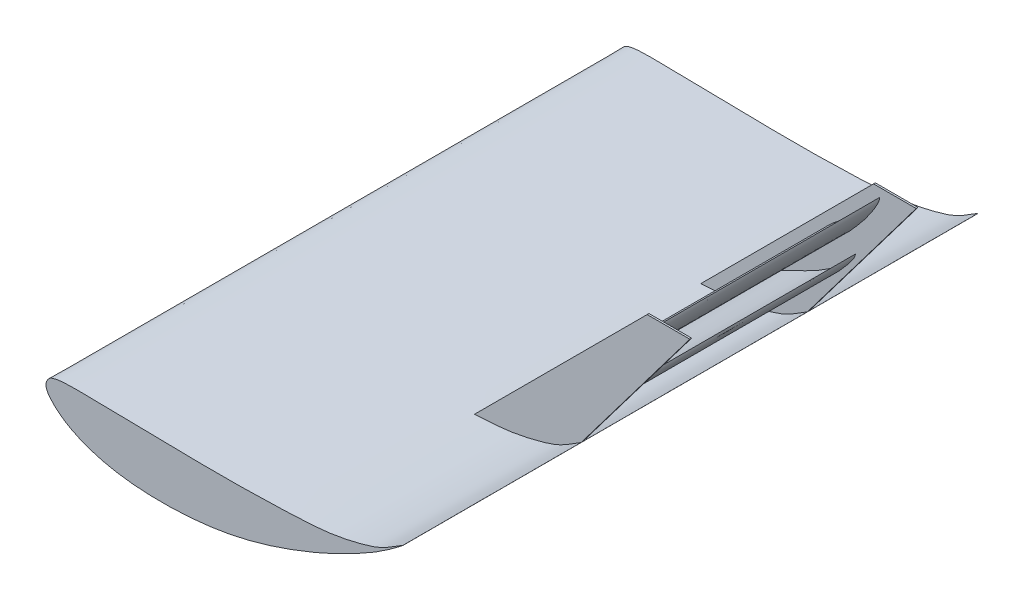
SolidWorks part; units mm, degrees
ref_plane "Front Plane" through (0, 0, 0) normal (0, 0, 1) x (1, 0, 0)
ref_plane "Top Plane" through (0, 0, 0) normal (0, 1, 0) x (1, 0, 0)
ref_plane "Right Plane" through (0, 0, 0) normal (1, 0, 0) x (0, 0, -1)
sketch "Sketch1" plane through (0, 0, 0) normal (0, 0, 1) x (1, 0, 0)
  line L0 (0, 0) -> (100, 0) construction
  line L1 (1.25, 16.6531) -> (1.25, -38.4553) construction
  line L2 (2.5, 17.9055) -> (2.5, -38.4614) construction
  line L3 (0, 16.6233) -> (0, -25.6938) construction
  line L4 (2.5, -38.4553) -> (2.5, 17.9055) construction
  line L6 (5, 17.9055) -> (5, -38.4553) construction
  line L8 (7.5, -38.4553) -> (7.5, 17.9055) construction
  line L10 (10, 17.9055) -> (10, -38.4553) construction
  line L12 (15, -38.4553) -> (15, 17.9055) construction
  line L14 (20, 17.9055) -> (20, -38.4553) construction
  line L16 (30, -38.4553) -> (30, 17.9055) construction
  line L18 (40, 17.9055) -> (40, -38.4553) construction
  line L20 (50, -38.4553) -> (50, 17.9055) construction
  line L22 (60, 17.9055) -> (60, -38.4553) construction
  line L24 (70, -38.4553) -> (70, 17.9055) construction
  line L26 (80, 17.9055) -> (80, -38.4553) construction
  line L28 (90, -38.4553) -> (90, 17.9055) construction
  line L30 (95, 17.9055) -> (95, -38.4553) construction
  line L32 (100, -38.4553) -> (100, 17.9055) construction
  spline S2 degree 3 poles (94.3673, -3.5638) (102.8561, 1.5222) (94.504, -2.988) (88.8138, -4.3065) (79.9056, -5.4947) (70.0198, -5.0741) (59.9849, -4.387) (49.9902, -3.5342) (39.9927, -2.4103) (30.0039, -1.1606) (21.6652, -0.2167) (14.9997, 0.5924) (10.0103, 1.184) (5.8366, 1.6528) (2.898, 1.5692) (0.8648, 1.1108) (-0.6238, -1.2668) (0.9385, -3.7627) (2.7533, -5.9838) (4.8768, -7.8493) (7.4255, -9.5789) (10.7358, -11.3943) (14.9019, -13.1207) (21.5668, -15.0457) (29.9416, -16.4142) (39.9918, -17.0298) (50.051, -16.6825) (60.0771, -15.2123) (70.1301, -12.7919) (80.007, -9.774) (88.8716, -6.1499) (94.3673, -3.5638) (102.8561, 1.5222) (94.504, -2.988) knots -0.105257 -0.054131 -0.027635 0 0.026268 0.051016 0.098804 0.146246 0.193788 0.241403 0.289125 0.336907 0.384666 0.408554 0.432437 0.456234 0.468112 0.474323 0.485191 0.50162 0.510955 0.52691 0.541278 0.554823 0.580548 0.60527 0.653411 0.700937 0.748406 0.796324 0.845052 0.894743 0.945869 0.972365 1 1.026268 1.051016 1.098804 only from (100, -0.1) to (100, -0.1)
  point P37 (0, -0.86)
  point P38 (1.25, -4.09)
  point P40 (1.25, 1.06)
  point P41 (2.5, 1.45)
  point P42 (5, -7.86)
  point P43 (2.5, -5.61)
  point P44 (5, 1.59)
  point P45 (7.5, -9.57)
  point P46 (7.5, 1.44)
  point P47 (10, 1.18)
  point P48 (15, 0.59)
  point P49 (15, -13.05)
  point P50 (20, -0.01)
  point P51 (20, -14.52)
  point P52 (30, -1.18)
  point P53 (30, -16.25)
  point P54 (40, -2.39)
  point P55 (10, -10.95)
  point P56 (40, -16.87)
  point P57 (40, -2.39)
  point P58 (50, -3.49)
  point P59 (50, -16.5)
  point P60 (60, -4.36)
  point P61 (60, -15.07)
  point P62 (70, -5.03)
  point P63 (70, -12.72)
  point P64 (80, -5.19)
  point P65 (80, -9.6)
  point P66 (90, -3.97)
  point P67 (90, -5.58)
  point P68 (95, -2.48)
  point P69 (95, -3.09)
  point P70 (100, -0.1)
  point P71 (100, -0.2)
  dimension "D1" = 100
  dimension "D2" = 1.25
  dimension "D3" = 2.5
  dimension "D4" = 2.5
  dimension "D5" = 7.5
  dimension "D6" = 10
  dimension "D7" = 15
  dimension "D8" = 5
  dimension "D9" = 10
  dimension "D10" = 10
  dimension "D11" = 10
  dimension "D12" = 10
  dimension "D13" = 10
  dimension "D14" = 10
  dimension "D15" = 10
  dimension "D16" = 5
  dimension "D17" = 5
curve "Curve1"
  spline degree 3 poles (98.5502, -0.8292, 0) (100.5299, 0.3794, 0) (99.1462, -0.6768, 0) (98.4443, -1.2755, 0) (97.3097, -2.0642, 0) (96.0009, -2.7117, 0) (94.4298, -3.3947, 0) (92.569, -4.0837, 0) (90.4012, -4.8122, 0) (87.9505, -5.5478, 0) (85.2749, -6.304, 0) (82.4359, -7.0338, 0) (79.5022, -7.7406, 0) (76.5208, -8.4057, 0) (73.5219, -9.0393, 0) (70.5175, -9.6161, 0) (67.5077, -10.1489, 0) (64.4881, -10.6321, 0) (61.4395, -11.0484, 0) (58.3521, -11.4274, 0) (55.2125, -11.781, 0) (52.0112, -12.0861, 0) (48.7533, -12.37, 0) (45.4544, -12.6663, 0) (42.1402, -12.9291, 0) (38.8572, -13.1898, 0) (35.6511, -13.4329, 0) (32.5711, -13.6325, 0) (29.6613, -13.7858, 0) (26.9506, -13.8772, 0) (24.4353, -13.8571, 0) (22.088, -13.7476, 0) (19.8826, -13.5013, 0) (17.7867, -13.168, 0) (15.7934, -12.7056, 0) (13.8906, -12.1349, 0) (12.076, -11.4655, 0) (10.3558, -10.6964, 0) (8.7488, -9.8421, 0) (7.2684, -8.933, 0) (5.9416, -8.0004, 0) (4.7755, -7.0863, 0) (3.7847, -6.217, 0) (2.957, -5.4094, 0) (2.269, -4.6735, 0) (1.728, -3.9816, 0) (1.2751, -3.3596, 0) (0.9309, -2.7719, 0) (0.6318, -2.2442, 0) (0.4105, -1.7465, 0) (0.2408, -1.2843, 0) (0.1068, -0.8552, 0) (0.0223, -0.45, 0) (-0.004, -0.0672, 0) (-0.0039, 0.3013, 0) (0.0809, 0.6622, 0) (0.2952, 0.9824, 0) (0.6315, 1.1995, 0) (1.032, 1.3336, 0) (1.4872, 1.4186, 0) (2.0055, 1.4764, 0) (2.6028, 1.5163, 0) (3.3032, 1.5313, 0) (4.1367, 1.5461, 0) (5.1573, 1.5223, 0) (6.4269, 1.4548, 0) (8.0274, 1.3654, 0) (10.0021, 1.2291, 0) (12.3384, 1.004, 0) (14.971, 0.7256, 0) (17.8195, 0.3367, 0) (20.844, -0.1077, 0) (24.0032, -0.6376, 0) (27.2668, -1.1722, 0) (30.5738, -1.7172, 0) (33.8785, -2.2723, 0) (37.1527, -2.7975, 0) (40.3807, -3.3138, 0) (43.5644, -3.7828, 0) (46.6972, -4.2145, 0) (49.7874, -4.5959, 0) (52.8339, -4.9281, 0) (55.8477, -5.1987, 0) (58.8316, -5.4085, 0) (61.7919, -5.5626, 0) (64.7329, -5.6385, 0) (67.6568, -5.6622, 0) (70.5644, -5.6128, 0) (73.4581, -5.4881, 0) (76.3366, -5.3163, 0) (79.1931, -5.05, 0) (82.0171, -4.7312, 0) (84.7804, -4.3625, 0) (87.434, -3.9036, 0) (89.9332, -3.4404, 0) (92.2075, -2.9247, 0) (94.233, -2.3848, 0) (95.9446, -1.8589, 0) (97.5056, -1.2357, 0) (98.5502, -0.8292, 0) (100.5299, 0.3794, 0) (99.1462, -0.6768, 0) knots -0.020778 -0.013318 -0.006872 0 0.003934 0.00967 0.015849 0.022782 0.030794 0.040273 0.051195 0.063508 0.076888 0.09098 0.105453 0.12007 0.134692 0.149314 0.163846 0.178433 0.193072 0.207875 0.222946 0.238282 0.253894 0.269743 0.28568 0.30147 0.316872 0.331691 0.345638 0.35857 0.370496 0.381625 0.392182 0.402235 0.411978 0.42144 0.430647 0.439636 0.448385 0.456672 0.46448 0.47158 0.477867 0.483331 0.488125 0.492267 0.495894 0.499125 0.502007 0.504569 0.506909 0.509051 0.510997 0.512815 0.514533 0.516257 0.518043 0.519896 0.521872 0.524061 0.526511 0.529332 0.532624 0.536536 0.54126 0.547229 0.554731 0.564199 0.575553 0.588316 0.602079 0.616691 0.632061 0.647918 0.664017 0.680023 0.695872 0.71147 0.726804 0.741922 0.756725 0.771359 0.785775 0.800025 0.814163 0.828192 0.842121 0.856004 0.869802 0.883566 0.897265 0.910851 0.924235 0.937151 0.949387 0.960589 0.970563 0.979222 0.986682 0.993128 1 1.003934 1.00967 1.015849 periodic
sketch "Sketch2" plane through (0, 0, 0) normal (0, 0, 1) x (1, 0, 0)
  line L0 (331.6325, -0.1558) -> (-65.7962, -45.4371) construction
  line L1 (-65.7962, -45.4371) -> (-68.337, -23.1365) construction
  line L2 (0, 0) -> (60.5483, 0) construction
  line L3 (385.2571, 82.501) -> (286.9589, 13.6718) construction
  line L4 (286.9589, 13.6718) -> (272.478, 34.3526) construction
  line L5 (331.6325, -0.1558) -> (331.6325, 76.9311) construction
  line L6 (331.6325, -0.1558) -> (397.2706, -0.1558) construction
  line L7 (412.1546, 150.4845) -> (355.5861, 93.9159) construction
  line L8 (299.294, 9.8442) -> (308.8152, 9.8442) construction
  line L9 (286.6325, 14.5606) -> (286.6325, 26.1748) construction
  line L10 (355.5861, 93.9159) -> (325.5679, 123.9341) construction
  line L11 (385.2571, 82.501) -> (439.2948, 82.501) construction
  line L12 (385.2571, 82.501) -> (385.2571, 253.7541) construction
  line L14 (360.5365, 92.501) -> (347.2815, 92.501) construction
  line L15 (355.2571, 94.5953) -> (355.2571, 86.9128) construction
  spline S1 degree 3 poles (384.8846, 81.2478) (385.5164, 83.2388) (384.4039, 80.6874) (383.6577, 79.5684) (382.5534, 77.8807) (381.234, 76.1849) (379.6159, 74.2589) (377.7366, 72.1854) (375.6004, 70.0085) (373.3094, 67.7296) (370.8484, 65.4636) (368.2936, 63.2048) (365.6704, 60.9752) (362.9606, 58.8233) (360.2036, 56.7073) (357.3809, 54.6556) (354.4918, 52.6644) (351.55, 50.7129) (348.5353, 48.8248) (345.4591, 46.9752) (342.3116, 45.1647) (339.0895, 43.3924) (335.7907, 41.6382) (332.4153, 39.904) (328.9642, 38.1714) (325.437, 36.4548) (321.8583, 34.7152) (318.229, 32.9837) (314.6045, 31.2409) (311.0296, 29.5177) (307.5607, 27.8619) (304.283, 26.2148) (301.2163, 24.6344) (298.438, 23.0944) (295.9876, 21.7059) (293.9535, 20.4794) (292.3194, 19.4647) (291.0255, 18.6563) (290.0064, 17.9765) (289.1977, 17.3878) (288.5198, 16.8905) (287.9605, 16.4397) (287.4911, 16.026) (287.1025, 15.6288) (286.8013, 15.2211) (286.6204, 14.7762) (286.6306, 14.3139) (286.7959, 13.9009) (287.0496, 13.5387) (287.3391, 13.1808) (287.7014, 12.8408) (288.1286, 12.5116) (288.6138, 12.1745) (289.1741, 11.8379) (289.8315, 11.5255) (290.5746, 11.1852) (291.4481, 10.8861) (292.4563, 10.579) (293.6392, 10.33) (295.0088, 10.1068) (296.5811, 9.9353) (298.3566, 9.8405) (300.3027, 9.8384) (302.3835, 9.9651) (304.5509, 10.2329) (306.7709, 10.6623) (309.0149, 11.2548) (311.2776, 12.005) (313.5546, 12.9239) (315.8434, 14.0403) (318.1798, 15.3178) (320.5616, 16.8273) (323.0467, 18.5404) (325.647, 20.4977) (328.4002, 22.653) (331.2889, 24.971) (334.2713, 27.4186) (337.3173, 29.9365) (340.3924, 32.4781) (343.4295, 35.0419) (346.4347, 37.5652) (349.3698, 40.0706) (352.2108, 42.5809) (354.9831, 45.0803) (357.6916, 47.5896) (360.3254, 50.1446) (362.9155, 52.7417) (365.4699, 55.3783) (367.9798, 58.0668) (370.4509, 60.7742) (372.8463, 63.4898) (375.1328, 66.1627) (377.2406, 68.7489) (379.1415, 71.1601) (380.7696, 73.3693) (382.1232, 75.3282) (383.1961, 77.0817) (384.0359, 78.6195) (384.6074, 80.1761) (384.8846, 81.2478) (385.5164, 83.2388) (384.4039, 80.6874) knots -0.015849 -0.00967 -0.003934 0 0.006872 0.013318 0.020778 0.029437 0.039411 0.050613 0.062849 0.075765 0.089149 0.102735 0.116434 0.130198 0.143996 0.157879 0.171808 0.185837 0.199975 0.214225 0.228641 0.243275 0.258078 0.273196 0.28853 0.304128 0.319977 0.335983 0.352082 0.367939 0.383309 0.397921 0.411684 0.424447 0.435801 0.445269 0.452771 0.45874 0.463464 0.467376 0.470668 0.473489 0.475939 0.478128 0.480104 0.481957 0.483743 0.485467 0.487185 0.489003 0.490949 0.493091 0.495431 0.497993 0.500875 0.504106 0.507733 0.511875 0.516669 0.522133 0.52842 0.53552 0.543328 0.551615 0.560364 0.569353 0.57856 0.588022 0.597765 0.607818 0.618375 0.629504 0.64143 0.654362 0.668309 0.683128 0.69853 0.71432 0.730257 0.746106 0.761718 0.777054 0.792125 0.806928 0.821567 0.836154 0.850686 0.865308 0.87993 0.894547 0.90902 0.923112 0.936492 0.948805 0.959727 0.969206 0.977218 0.984151 0.99033 0.996066 1 1.006872 1.013318 1.020778 only from (385.2571, 82.501) to (385.2571, 82.501)
  spline S2 degree 3 poles (310.6391, -16.2329) (342.3319, 7.4626) (310.948, -13.8864) (288.8507, -21.4531) (253.8988, -29.8144) (214.402, -32.1744) (174.2032, -33.5355) (134.0967, -34.2209) (93.8685, -33.8291) (53.6236, -32.9335) (20.0676, -32.5806) (-6.7778, -32.082) (-26.867, -31.764) (-43.661, -31.6021) (-55.3165, -33.1337) (-63.2173, -35.7866) (-68.169, -45.8522) (-60.9356, -55.1433) (-52.8102, -63.238) (-43.602, -69.7925) (-32.7577, -75.633) (-18.8487, -81.5041) (-1.572, -86.6718) (25.7261, -91.6102) (59.5991, -93.6371) (99.8297, -91.9854) (139.7029, -86.4995) (178.9865, -76.5608) (217.9897, -62.8307) (256.0482, -46.7957) (289.8325, -28.7623) (310.6391, -16.2329) (342.3319, 7.4626) (310.948, -13.8864) knots -0.105257 -0.054131 -0.027635 0 0.026268 0.051016 0.098804 0.146246 0.193788 0.241403 0.289125 0.336907 0.384666 0.408554 0.432437 0.456234 0.468112 0.474323 0.485191 0.50162 0.510955 0.52691 0.541278 0.554823 0.580548 0.60527 0.653411 0.700937 0.748406 0.796324 0.845052 0.894743 0.945869 0.972365 1 1.026268 1.051016 1.098804 only from (331.6325, -0.1558) to (331.6325, -0.1558)
  spline S3 degree 3 poles (412.0551, 149.6186) (412.2394, 150.9988) (411.8044, 149.195) (411.444, 148.3739) (410.9144, 147.1381) (410.2444, 145.8719) (409.4051, 144.4202) (408.4113, 142.8413) (407.2608, 141.1648) (406.0205, 139.4033) (404.6671, 137.6307) (403.2512, 135.852) (401.7872, 134.0845) (400.2572, 132.358) (398.692, 130.6496) (397.0763, 128.9757) (395.41, 127.334) (393.7045, 125.7123) (391.9439, 124.1236) (390.1384, 122.5532) (388.2815, 121.0002) (386.3712, 119.4635) (384.4085, 117.9299) (382.3932, 116.4006) (380.328, 114.8636) (378.211, 113.3282) (376.0628, 111.7718) (373.8805, 110.2149) (371.7026, 108.6511) (369.5551, 107.1059) (367.4692, 105.6172) (365.508, 104.1564) (363.6776, 102.7638) (362.0318, 101.4311) (360.5837, 100.2358) (359.3903, 99.1951) (358.4349, 98.3397) (357.6789, 97.6592) (357.0886, 97.0949) (356.6258, 96.6148) (356.2383, 96.2098) (355.9233, 95.8491) (355.663, 95.5231) (355.4538, 95.2174) (355.3033, 94.9148) (355.236, 94.6018) (355.2962, 94.2995) (355.4525, 94.0475) (355.6611, 93.839) (355.8926, 93.6376) (356.1697, 93.4563) (356.4883, 93.2896) (356.846, 93.1244) (357.2528, 92.9683) (357.7205, 92.8393) (358.2478, 92.7019) (358.8559, 92.6067) (359.5534, 92.5218) (360.3589, 92.4952) (361.2839, 92.5073) (362.336, 92.5766) (363.5127, 92.72) (364.7906, 92.9439) (366.142, 93.2679) (367.534, 93.6947) (368.9418, 94.2336) (370.3465, 94.8823) (371.7452, 95.6368) (373.1338, 96.5037) (374.5072, 97.5017) (375.8933, 98.6108) (377.2822, 99.8777) (378.7155, 101.29) (380.1961, 102.8761) (381.7542, 104.6099) (383.3824, 106.4662) (385.0571, 108.4184) (386.7654, 110.4241) (388.4901, 112.4487) (390.1873, 114.4835) (391.8682, 116.4881) (393.5052, 118.4728) (395.0798, 120.4498) (396.6106, 122.4116) (398.0983, 124.3726) (399.5317, 126.355) (400.9316, 128.3599) (402.3034, 130.3867) (403.6401, 132.4423) (404.949, 134.5059) (406.2072, 136.5661) (407.399, 138.5857) (408.4835, 140.5277) (409.4524, 142.3307) (410.2655, 143.9697) (410.9274, 145.4124) (411.4289, 146.6879) (411.8022, 147.7947) (411.9972, 148.8829) (412.0551, 149.6186) (412.2394, 150.9988) (411.8044, 149.195) knots -0.015849 -0.00967 -0.003934 0 0.006872 0.013318 0.020778 0.029437 0.039411 0.050613 0.062849 0.075765 0.089149 0.102735 0.116434 0.130198 0.143996 0.157879 0.171808 0.185837 0.199975 0.214225 0.228641 0.243275 0.258078 0.273196 0.28853 0.304128 0.319977 0.335983 0.352082 0.367939 0.383309 0.397921 0.411684 0.424447 0.435801 0.445269 0.452771 0.45874 0.463464 0.467376 0.470668 0.473489 0.475939 0.478128 0.480104 0.481957 0.483743 0.485467 0.487185 0.489003 0.490949 0.493091 0.495431 0.497993 0.500875 0.504106 0.507733 0.511875 0.516669 0.522133 0.52842 0.53552 0.543328 0.551615 0.560364 0.569353 0.57856 0.588022 0.597765 0.607818 0.618375 0.629504 0.64143 0.654362 0.668309 0.683128 0.69853 0.71432 0.730257 0.746106 0.761718 0.777054 0.792125 0.806928 0.821567 0.836154 0.850686 0.865308 0.87993 0.894547 0.90902 0.923112 0.936492 0.948805 0.959727 0.969206 0.977218 0.984151 0.99033 0.996066 1 1.006872 1.013318 1.020778 only from (412.1546, 150.4845) to (412.1546, 150.4845)
  dimension "D2" = 400
  dimension "D1" = 90
  dimension "D3" = 6.5
  dimension "D4" = 90
  dimension "D5" = 120
  dimension "D6" = 35
  dimension "D7" = 10
  dimension "D8" = 45
  dimension "D9" = 90
  dimension "D10" = 80
  dimension "D11" = 45
  dimension "D12" = 30
  dimension "D13" = 10
extrude "Boss-Extrude1" add sketch "Sketch2" along normal blind 450 and the other way blind 190 contours S2
extrude "Boss-Extrude2" add sketch "Sketch2<3>" along normal blind 250 separate body contours S1
sketch "Sketch2<3>" plane through (0, 0, 0) normal (0, 0, 1) x (1, 0, 0) same geometry as "Sketch2"
extrude "Boss-Extrude3" add sketch "Sketch2<4>" along normal blind 250 separate body contours S3
sketch "Sketch2<4>" plane through (0, 0, 0) normal (0, 0, 1) x (1, 0, 0) same geometry as "Sketch2"
sketch "Sketch3" plane through (0, 0, 0) normal (0, 0, 1) x (1, 0, 0)
  line L0 (213.126, -32.0618) -> (405.3691, 160.1813)
  line L1 (405.3691, 160.1813) -> (452.8645, 160.1813)
  line L2 (452.8645, 160.1813) -> (331.6325, -0.1558)
  spline S0 degree 3 poles (310.6391, -16.2329) (342.3319, 7.4626) (310.948, -13.8864) (288.8507, -21.4531) (253.8988, -29.8144) (214.402, -32.1744) (174.2032, -33.5355) (134.0967, -34.2209) (93.8685, -33.8291) (53.6236, -32.9335) (20.0676, -32.5806) (-6.7778, -32.082) (-26.867, -31.764) (-43.661, -31.6021) (-55.3165, -33.1337) (-63.2173, -35.7866) (-68.169, -45.8522) (-60.9356, -55.1433) (-52.8102, -63.238) (-43.602, -69.7925) (-32.7577, -75.633) (-18.8487, -81.5041) (-1.572, -86.6718) (25.7261, -91.6102) (59.5991, -93.6371) (99.8297, -91.9854) (139.7029, -86.4995) (178.9865, -76.5608) (217.9897, -62.8307) (256.0482, -46.7957) (289.8325, -28.7623) (310.6391, -16.2329) (342.3319, 7.4626) (310.948, -13.8864) knots -0.105257 -0.054131 -0.027635 0 0.026268 0.051016 0.098804 0.146246 0.193788 0.241403 0.289125 0.336907 0.384666 0.408554 0.432437 0.456234 0.468112 0.474323 0.485191 0.50162 0.510955 0.52691 0.541278 0.554823 0.580548 0.60527 0.653411 0.700937 0.748406 0.796324 0.845052 0.894743 0.945869 0.972365 1 1.026268 1.051016 1.098804 only from (331.6325, -0.1558) to (331.6325, -0.1558) construction
  spline S1 degree 3 poles (331.6325, -0.1558) (331.3048, -0.0386) (310.948, -13.8864) (288.8507, -21.4531) (253.8988, -29.8144) (227.165, -31.4118) (213.5191, -32.0438) (213.126, -32.0618) knots 0 0 0 0 0.026268 0.051016 0.098804 0.146246 0.147653 0.147653 0.147653 0.147653
extrude "Boss-Extrude4" add sketch "Sketch3" against normal blind 2
ref_plane "Plane1" through (0, 0, 125) normal (0, 0, 1) x (1, 0, 0)
mirror "Mirror1" about plane through (0, 0, 125) normal (0, 0, 1) of "Boss-Extrude4"
ref_plane "Plane4" through (0, 0, -190) normal (0, 0, 1) x (1, 0, 0)
